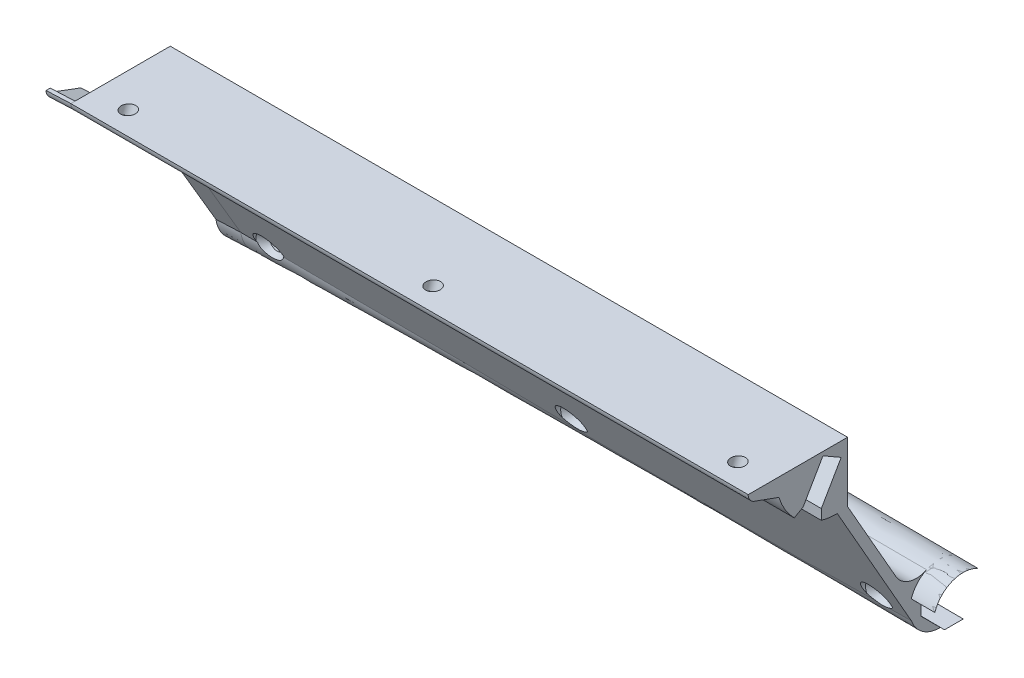
SolidWorks part; units mm, degrees
ref_plane "Front Plane" through (0, 0, 0) normal (0, 0, 1) x (1, 0, 0)
ref_plane "Top Plane" through (0, 0, 0) normal (0, 1, 0) x (1, 0, 0)
ref_plane "Right Plane" through (0, 0, 0) normal (1, 0, 0) x (0, 0, -1)
sketch "Sketch1" plane through (0, 0, 0) normal (1, 0, 0) x (0, 0, -1)
  line L0 (-1066.8, -7.5565) -> (1066.8, -7.5565) construction
  line L1 (-101.6, -49.3897) -> (-101.6, -134.0913) construction
  point P0 (-129.3085, -7.5565)
  line B0 (-152.0053, -9.9433) -> (-145.3394, -12.3695)
  line B1 (-138.7918, -17.8795) -> (-133.4197, -8.5759)
  line B2 (-133.4197, -8.5759) -> (-128.4924, -11.4203)
  line B3 (-128.4924, -11.4203) -> (-133.8645, -20.724)
  line B4 (-138.7918, -17.8795) -> (-141.1886, -19.2631)
  line B5 (-151.1366, -10.0965) -> (-145.86, -10.0965)
  line B6 (-146.0566, -7.5565) -> (-153.6766, -7.5565)
  line B7 (-146.0566, -7.5565) -> (-126.7512, -7.5565)
  line B8 (-126.7512, -23.8281) -> (-126.7512, -7.5565)
  line B9 (-133.8645, -20.724) -> (-133.8646, -23.4918)
  arc B10 (-145.86, -10.0965) -> (-141.1886, -19.2631) centre (-129.5466, -7.5565) ccw
  arc B11 (-153.6766, -7.5565) -> (-151.1366, -10.0965) centre (-151.1366, -7.5565) ccw
  arc B12 (-133.8646, -23.4918) -> (-126.7512, -23.8281) centre (-129.5466, -7.5565) ccw
  dimension "D1" = 25.1512
sketch_block_instance "Rear LED Sketch Block1-1"
sketch_block "Rear LED Sketch Block1" parameters "D1"=20
extrude "Boss-Extrude1" add sketch "Sketch1" along normal mid plane 190.5 contours B9 B12 B8 B7 B6 B11 B5 B10 B4 B1 B2 B3 | B11 B0 B10 B5
sketch "Sketch4" plane through (0, 0, 0) normal (1, 0, 0) x (0, 0, -1)
  line L0 (-106.68, -54.2581) -> (-101.6, -54.2581)
  line L1 (-106.68, -54.2581) -> (-101.6, -54.2581)
  line L2 (-106.68, -54.2581) -> (-106.68, -58.9572)
  line L3 (-106.68, -54.2581) -> (-106.68, -58.9572)
sketch "Sketch2" plane through (0, 0, 0) normal (1, 0, 0) x (0, 0, -1)
  line L2 (-106.68, -54.2581) -> (-101.6, -54.2581) construction
  line L3 (-106.68, -54.2581) -> (-106.68, -58.9572) construction
  line B0 (-101.7905, -59.1476) -> (-101.7905, -64.4689)
  line B1 (-101.7905, -59.1476) -> (-106.8705, -59.1476)
  line B2 (-106.8705, -54.0676) -> (-106.8705, -59.1476)
  line B3 (-106.8705, -54.0676) -> (-101.7905, -54.0676)
  line B4 (-101.7905, -49.2924) -> (-101.7905, -54.0676)
  line B5 (-101.7905, -49.2924) -> (-97.79, -49.2924)
  arc B6 (-97.79, -49.2924) -> (-101.7905, -64.4689) centre (-101.7905, -56.3534) ccw
  dimension "D1" = 0.1905
  dimension "D2" = 0.1905
sketch_block_instance "Rear LED Sketch Block2-1"
sketch_block "Rear LED Sketch Block2"
sketch "Sketch3" plane through (0, 0, 101.6) normal (0, 0, 1) x (1, 0, 0)
  arc A0 (372.8943, -70.8558) -> (-885.4187, -145.1541) centre (30.2426, -4960.2394) ccw construction
  arc A1 (372.8943, -70.8558) -> (-885.4187, -145.1541) centre (30.2426, -4960.2394) ccw
sweep "Sweep1" add profiles "Sketch2" path "Sketch3"
ref_plane "Plane1" through (-95.25, 0, 0) normal (-1, 0, 0) x (0, 0, 1)
ref_plane "Plane2" through (95.25, 0, 0) normal (1, 0, 0) x (0, 0, -1)
other "SurfaceCut1"
other "SurfaceCut3"
ref_plane "Plane4" through (-94.6651, -4.0865, 0) normal (0.9991, 0.0431, 0) x (0, 0, -1)
sketch "Sketch5" plane through (0, 0, 0) normal (1, 0, 0) x (0, 0, -1)
  line L0 (-129.675, -23.8281) -> (-108.8408, -60.3728)
  line L1 (-106.8705, -58.7002) -> (-126.7512, -23.8281)
  line L2 (-126.7512, -23.8281) -> (-126.7512, -7.5565) construction
  line L3 (-126.7512, -23.8281) -> (-129.675, -23.8281)
  line L4 (-108.8408, -60.3728) -> (-106.8705, -60.3728)
  line L5 (-106.8705, -60.3728) -> (-106.8705, -58.7002)
  line L6 (-106.8705, -54.0676) -> (-106.8705, -59.1476) construction
  arc A0 (-97.79, -49.2924) -> (-101.7905, -64.4689) centre (-101.7905, -56.3534) ccw construction
  dimension "D1" = 2.54
extrude "Boss-Extrude2" add sketch "Sketch5" along normal up to surface and the other way up to surface
other "SurfaceCut5"
sketch "Sketch6" plane through (-94.6651, -4.0865, 0) normal (-0.9991, -0.0431, 0) x (0, 0, 1)
  line L0 (101.7905, -56.5507) -> (101.7905, -61.8728) construction
  line L1 (153.6766, -3.4732) -> (126.7512, -3.4732) construction
  line L2 (152.0053, -5.8623) -> (145.3394, -8.2907) construction
  line L3 (129.5391, -19.9986) -> (109.8687, -54.534) construction
  line L4 (101.7905, -56.5507) -> (101.7905, -61.8728)
  line L5 (153.6766, -3.4732) -> (126.7512, -3.4732)
  line L6 (152.0053, -5.8623) -> (145.3394, -8.2907)
  line L7 (129.5391, -19.9986) -> (109.8687, -54.534)
  line L8 (128.8829, -18.8412) -> (108.7495, -54.1895)
  line L9 (151.614, -4.7883) -> (144.4001, -7.4164)
  line L10 (138.7918, -13.8058) -> (141.1886, -15.1907) construction
  line L11 (133.8645, -16.6529) -> (133.8646, -19.4234) construction
  line L12 (140.1634, -14.5984) -> (141.1886, -15.1907)
  line L13 (133.8646, -18.2391) -> (133.8646, -19.4234)
  line L14 (133.5654, -18.3202) -> (133.8646, -18.2391)
  line L15 (140.3822, -14.3806) -> (140.1634, -14.5984)
  ellipse E0 centre (151.1366, -3.4732) end of major axis (151.1366, -0.9308) minor radius 2.54 (152.0053, -5.8623) -> (153.6766, -3.4732) ccw construction
  ellipse E1 centre (129.5466, -3.4732) end of major axis (129.5466, -19.9986) minor radius 16.51 (141.1886, -15.1907) -> (145.3394, -8.2907) ccw construction
  ellipse E2 centre (129.5466, -3.4732) end of major axis (129.5466, -19.9986) minor radius 16.51 (129.5391, -19.9986) -> (133.8646, -19.4234) ccw construction
  ellipse E3 centre (151.1366, -3.4732) end of major axis (151.1366, -0.9308) minor radius 2.54 (152.0053, -5.8623) -> (153.6766, -3.4732) ccw
  ellipse E4 centre (129.5466, -3.4732) end of major axis (129.5466, -19.9986) minor radius 16.51 (141.1886, -15.1907) -> (145.3394, -8.2907) ccw
  ellipse E5 centre (129.5466, -3.4732) end of major axis (129.5466, -19.9986) minor radius 16.51 (129.5391, -19.9986) -> (133.8646, -19.4234) ccw
  spline S0 degree 3 poles (-155.2589, 904.5233) (13.2066, 99.2717) (72.9154, -67.3921) (103.5206, -61.6901) (103.7625, -61.6335) (104.2426, -61.4975) (104.4819, -61.4176) (105.1825, -61.1468) (105.6271, -60.9257) (106.2612, -60.5347) (106.467, -60.3945) (106.8673, -60.0935) (107.0617, -59.9327) (107.6156, -59.4296) (107.9506, -59.0637) (108.5527, -58.2714) (108.8209, -57.8411) (109.2671, -56.9519) (109.4481, -56.4899) (115.3533, -36.0633) (46.0699, 14.3305) (-367.4461, -933.2399) knots -7.656413 -7.656413 -7.656413 -7.656413 0.125 0.125 0.1875 0.1875 0.25 0.25 0.375 0.375 0.4375 0.4375 0.5 0.5 0.625 0.625 0.75 0.75 0.875 0.875 6.076436 6.076436 6.076436 6.076436 only from (101.7905, -61.8728) to (109.8687, -54.534) construction
  spline S1 degree 3 poles (101.7905, -61.8728) (102.2937, -61.8728) (102.789, -61.8264) (103.5206, -61.6901) (103.7625, -61.6335) (104.2426, -61.4975) (104.4819, -61.4176) (105.1825, -61.1468) (105.6271, -60.9257) (106.2612, -60.5347) (106.467, -60.3945) (106.8673, -60.0935) (107.0617, -59.9327) (107.6156, -59.4296) (107.9506, -59.0637) (108.5527, -58.2714) (108.8209, -57.8411) (109.2671, -56.9519) (109.4481, -56.4899) (109.7253, -55.5312) (109.8205, -55.0342) (109.8687, -54.534) knots 0 0 0 0 0.125 0.125 0.1875 0.1875 0.25 0.25 0.375 0.375 0.4375 0.4375 0.5 0.5 0.625 0.625 0.75 0.75 0.875 0.875 1 1 1 1
  spline S2 degree 1 poles (101.7905, -60.7298) (108.7495, -54.1895) knots 0 0 1 1 construction
  spline S3 degree 1 poles (128.8829, -18.8412) (133.5654, -18.3202) knots 0 0 1 1 construction
  spline S4 degree 3 poles (101.7905, -60.7298) (102.6619, -60.7298) (104.4225, -60.3954) (106.6781, -58.9596) (108.2494, -56.8015) (108.6958, -55.0607) (108.7495, -54.1895) knots 0 0 0 0 0.255705 0.511411 0.767116 1.022822 1.022822 1.022822 1.022822
  spline S5 degree 3 poles (128.8829, -18.8412) (129.2766, -18.8583) (130.0657, -18.862) (131.2459, -18.7765) (132.4161, -18.6005) (133.1851, -18.4234) (133.5654, -18.3202) knots 3.09839 3.09839 3.09839 3.09839 3.175346 3.252302 3.329258 3.406214 3.406214 3.406214 3.406214
  spline S6 degree 1 poles (140.3822, -14.3806) (144.4001, -7.4164) knots 0 0 1 1 construction
  spline S7 degree 1 poles (151.614, -4.7883) (152.5336, -3.4732) knots 0 0 1 1 construction
  spline S8 degree 3 poles (140.3822, -14.3806) (140.8622, -13.9028) (141.76, -12.8825) (142.8926, -11.1885) (143.7924, -9.3599) (144.2266, -8.0713) (144.4001, -7.4164) knots -2.35896 -2.35896 -2.35896 -2.35896 -2.226725 -2.09449 -1.962254 -1.830019 -1.830019 -1.830019 -1.830019
  spline S9 degree 3 poles (151.614, -4.7883) (151.7472, -4.7398) (152.0001, -4.6011) (152.2985, -4.2888) (152.4897, -3.9012) (152.5336, -3.6152) (152.5336, -3.4732) knots -2.792527 -2.792527 -2.792527 -2.792527 -2.487094 -2.181662 -1.876229 -1.570796 -1.570796 -1.570796 -1.570796
  dimension "D1" = 1.143
extrude "Boss-Extrude3" add sketch "Sketch6" along normal offset from surface (6.731 mm away) 0.381
sketch "Sketch7" plane through (95.25, 0, 0) normal (1, 0, 0) x (0, 0, -1)
  line L16 (-129.5391, -24.0665) -> (-109.5074, -59.2035)
  line L17 (-101.7905, -64.8071) -> (-101.7905, -59.4854)
  line L18 (-101.7905, -59.4854) -> (-106.8705, -59.4854)
  line L19 (-106.8705, -59.4854) -> (-106.8705, -54.4051)
  line L22 (-106.8705, -54.4051) -> (-101.7905, -54.4051)
  line L24 (-101.7905, -54.4051) -> (-101.7905, -49.6295)
  line L26 (-101.7905, -49.6295) -> (-97.79, -49.6295)
  line L27 (-109.4857, -54.113) -> (-126.7512, -23.8281)
  line L50 (-126.7512, -23.8281) -> (-126.7512, -7.5565)
  line L61 (-126.7512, -7.5565) -> (-153.6766, -7.5565)
  line L62 (-152.0053, -9.9433) -> (-145.3394, -12.3695)
  line L63 (-141.1886, -19.2631) -> (-138.7918, -17.8795)
  line L64 (-138.7918, -17.8795) -> (-133.4197, -8.5759)
  line L65 (-133.4197, -8.5759) -> (-128.4924, -11.4203)
  line L66 (-128.4924, -11.4203) -> (-133.8645, -20.724)
  line L67 (-133.8645, -20.724) -> (-133.8646, -23.4918)
  line L68 (-129.5391, -24.0665) -> (-109.5074, -59.2035)
  line L69 (-101.7905, -64.8071) -> (-101.7905, -59.4854)
  line L70 (-101.7905, -59.4854) -> (-106.8705, -59.4854)
  line L71 (-106.8705, -59.4854) -> (-106.8705, -54.4051)
  line L72 (-106.8705, -54.4051) -> (-101.7905, -54.4051)
  line L73 (-101.7905, -54.4051) -> (-101.7905, -49.6295)
  line L74 (-101.7905, -49.6295) -> (-97.79, -49.6295)
  line L75 (-109.4857, -54.113) -> (-126.7512, -23.8281)
  line L76 (-126.7512, -23.8281) -> (-126.7512, -7.5565)
  line L77 (-126.7512, -7.5565) -> (-153.6766, -7.5565)
  line L78 (-152.0053, -9.9433) -> (-145.3394, -12.3695)
  line L79 (-141.1886, -19.2631) -> (-138.7918, -17.8795)
  line L80 (-138.7918, -17.8795) -> (-133.4197, -8.5759)
  line L81 (-133.4197, -8.5759) -> (-128.4924, -11.4203)
  line L82 (-128.4924, -11.4203) -> (-133.8645, -20.724)
  line L83 (-133.8645, -20.724) -> (-133.8646, -23.4918)
  arc A9 (-153.6766, -7.5565) -> (-152.0053, -9.9433) centre (-151.1366, -7.5565) ccw
  arc A10 (-145.3394, -12.3695) -> (-141.1886, -19.2631) centre (-129.5466, -7.5565) ccw
  arc A11 (-133.8646, -23.4918) -> (-129.5391, -24.0665) centre (-129.5466, -7.5565) ccw
  arc A12 (-153.6766, -7.5565) -> (-152.0053, -9.9433) centre (-151.1366, -7.5565) ccw
  arc A13 (-145.3394, -12.3695) -> (-141.1886, -19.2631) centre (-129.5466, -7.5565) ccw
  arc A14 (-133.8646, -23.4918) -> (-129.5391, -24.0665) centre (-129.5466, -7.5565) ccw
  spline S2 degree 3 poles (2567.8604, 1289.2452) (833.2132, 493.0741) (-144.0017, 8.289) (-108.8291, -60.7533) (-108.6035, -61.1213) (-108.1037, -61.8086) (-107.8289, -62.13) (-107.3797, -62.5793) (-107.2238, -62.7236) (-106.8993, -63.0008) (-106.7303, -63.1339) (-106.2132, -63.5093) (-105.8522, -63.7302) (-105.0983, -64.1144) (-104.7029, -64.2785) (-41.9716, -84.6456) (151.7268, 666.5201) (589.7314, 2852.2044) knots -22.581561 -22.581561 -22.581561 -22.581561 0.125 0.125 0.25 0.25 0.375 0.375 0.4375 0.4375 0.5 0.5 0.625 0.625 0.75 0.75 19.917831 19.917831 19.917831 19.917831 only from (-109.5074, -59.2035) to (-101.7905, -64.8071)
  spline S3 degree 3 poles (-1033.1562, -2897.998) (-208.9033, -640.4241) (-44.6823, -65.5493) (-99.7186, -48.8382) (-100.012, -48.7666) (-100.5993, -48.6573) (-101.1886, -48.581) (-101.7821, -48.5695) (-102.3777, -48.5907) (-102.6784, -48.6181) (-103.5656, -48.7489) (-104.1393, -48.8995) (-104.9734, -49.2193) (-105.2487, -49.3426) (-105.7804, -49.6172) (-106.293, -49.9191) (-106.7683, -50.2741) (-107.2249, -50.6559) (-107.445, -50.8615) (-108.0664, -51.5105) (-108.4269, -51.9817) (-108.8886, -52.7452) (-109.0298, -53.0106) (-136.6979, -112.8086) (604.8792, -397.3944) (-3032.056, 599.2618) knots -11.847549 -11.847549 -11.847549 -11.847549 0.125 0.125 0.1875 0.1875 0.25 0.3125 0.3125 0.375 0.375 0.5 0.5 0.5625 0.5625 0.625 0.6875 0.6875 0.75 0.75 0.875 0.875 0.9375 0.9375 14.610125 14.610125 14.610125 14.610125 only from (-97.79, -49.6295) to (-109.4857, -54.113)
  spline S4 degree 3 poles (-109.5074, -59.2035) (-109.3761, -59.6067) (-109.2142, -59.9973) (-108.8291, -60.7533) (-108.6035, -61.1213) (-108.1037, -61.8086) (-107.8289, -62.13) (-107.3797, -62.5793) (-107.2238, -62.7236) (-106.8993, -63.0008) (-106.7303, -63.1339) (-106.2132, -63.5093) (-105.8522, -63.7302) (-105.0983, -64.1144) (-104.7029, -64.2785) (-103.4836, -64.6744) (-102.6483, -64.8071) (-101.7905, -64.8071) knots 0 0 0 0 0.125 0.125 0.25 0.25 0.375 0.375 0.4375 0.4375 0.5 0.5 0.625 0.625 0.75 0.75 1 1 1 1
  spline S5 degree 3 poles (-97.79, -49.6295) (-98.3134, -49.333) (-98.8611, -49.0986) (-99.7186, -48.8382) (-100.012, -48.7666) (-100.5993, -48.6573) (-101.1886, -48.581) (-101.7821, -48.5695) (-102.3777, -48.5907) (-102.6784, -48.6181) (-103.5656, -48.7489) (-104.1393, -48.8995) (-104.9734, -49.2193) (-105.2487, -49.3426) (-105.7804, -49.6172) (-106.293, -49.9191) (-106.7683, -50.2741) (-107.2249, -50.6559) (-107.445, -50.8615) (-108.0664, -51.5105) (-108.4269, -51.9817) (-108.8886, -52.7452) (-109.0298, -53.0106) (-109.2816, -53.5548) (-109.3915, -53.8316) (-109.4857, -54.113) knots 0 0 0 0 0.125 0.125 0.1875 0.1875 0.25 0.3125 0.3125 0.375 0.375 0.5 0.5 0.5625 0.5625 0.625 0.6875 0.6875 0.75 0.75 0.875 0.875 0.9375 0.9375 1 1 1 1
  dimension "D1" = 0
extrude "Cut-Extrude1" cut sketch "Sketch7" against normal blind 6.35
sketch "Sketch8" plane through (0, 0, 106.8705) normal (0, 0, -1) x (-1, 0, 0)
  arc A2 (92.2896, -58.0454) -> (-88.9304, -56.8655) centre (-30.2426, -4960.2394) ccw
  arc A3 (92.2896, -58.0454) -> (-88.9304, -56.8655) centre (-30.2426, -4960.2394) ccw
  point P0 (-80.8649, -56.7756)
  point P1 (1.6851, -56.6182)
  point P2 (84.2351, -57.8507)
  dimension "D2" = 82.55
  dimension "D3" = 82.55
  dimension "D1" = 2.54
sketch "Sketch9" plane through (0, 0, 106.8705) normal (0, 0, -1) x (-1, 0, 0)
  point P0 (-80.8649, -56.7756)
  point P1 (1.6851, -56.6182)
  point P3 (84.2351, -57.8507)
ref_plane "Plane5" through (80.8649, 0, 0) normal (1, 0, 0) x (0, 0, -1)
fillet "Fillet1" radius 6.35 1 edges at (46.559, -53.9689, 109.5678)
sketch "Sketch10" plane through (80.8649, 0, 0) normal (1, 0, 0) x (0, 0, -1)
  line L0 (-106.8705, -58.6806) -> (-106.8705, -56.7756)
  line L1 (-106.8705, -56.7756) -> (-113.2205, -56.7756)
  line L2 (-113.2205, -56.7756) -> (-113.2205, -60.5856)
  line L3 (-113.2205, -60.5856) -> (-110.0455, -60.5856)
  line L4 (-110.0455, -60.5856) -> (-108.1405, -58.6806)
  line L5 (-108.1405, -58.6806) -> (-106.8705, -58.6806)
  line L6 (-106.8705, -59.4854) -> (-106.8705, -54.4051) construction
  dimension "D1" = 45
  dimension "D2" = 1.905
  dimension "D3" = 3.81
  dimension "D4" = 1.27
  dimension "D5" = 6.35
revolve "Cut-Revolve1" cut sketch "Sketch10" angle 360 about L1
pattern_sketch "Sketch-Pattern1" of "Cut-Revolve1" driven by "Sketch9"
sketch "Sketch11" plane through (0, -57.6337, 20.977) normal (0, -0.9397, 0.342) x (1, 0, 0)
  line L0 (88.9, 135.8906) -> (-94.3599, 135.8906) construction
  line L1 (88.9, 139.4374) -> (88.9, 132.3438) construction
  line L2 (-94.4122, 139.4374) -> (-94.3075, 132.3438) construction
  point P6 (-2.7299, 135.8906)
  point P7 (79.8201, 135.8906)
  point P8 (-85.2799, 135.8906)
  dimension "D1" = 82.55
  dimension "D2" = 82.55
sketch "Sketch12" plane through (0, -57.6337, 20.977) normal (0, -0.9397, 0.342) x (1, 0, 0)
  point P0 (79.8201, 135.8906)
  point P1 (-2.7299, 135.8906)
  point P3 (-85.2799, 135.8906)
ref_plane "Plane6" through (-2.7299, 0, 0) normal (1, 0, 0) x (0, 0, -1)
sketch "Sketch13" plane through (-2.7299, 0, 0) normal (1, 0, 0) x (0, 0, -1)
  line L0 (-148.6724, -11.1564) -> (-147.125, -6.905)
  line L1 (-152.0053, -9.9433) -> (-145.3394, -12.3695) construction
  line L2 (-147.125, -6.905) -> (-145.3348, -7.5565)
  line L3 (-145.3348, -7.5565) -> (-146.2307, -10.0178)
  line L4 (-146.2307, -10.0178) -> (-145.0921, -12.4595)
  line L6 (-150.0381, -14.9088) -> (-148.6724, -11.1564)
  line L7 (-152.0053, -9.9433) -> (-145.3394, -12.3695) construction
  line L9 (-145.0921, -12.4595) -> (-146.4579, -16.2119)
  line L10 (-146.4579, -16.2119) -> (-150.0381, -14.9088)
  line L11 (-151.7328, -8.5112) -> (-144.3303, -11.2055) construction
  line L12 (-1093.7253, -7.5565) -> (-1066.8, -7.5565) construction
  point P4 (-148.9211, -10.9278)
  point P8 (-147.3298, -5.4676)
  point P13 (0, 0)
  point P16 (0, 0)
  dimension "D1" = 1.905
  dimension "D2" = 3.81
  dimension "D4" = 45
revolve "Cut-Revolve2" cut sketch "Sketch13" angle 360 about L6
pattern_sketch "Sketch-Pattern2" of "Cut-Revolve2" driven by "Sketch12"
sketch "Sketch14" plane through (0, 0, 126.7512) normal (0, 0, -1) x (-1, 0, 0)
  line L0 (79.6029, -10.0965) -> (-79.6029, -10.0965) construction
  line L1 (-88.9, -7.5565) -> (94.5153, -7.5565) construction
  text T0 "<b>Rear Ceiling LED Strip Mount 5 V1</b>" font "Century Gothic" height 5.08
  point P2 (0, -10.0965)
  point P3 (0, 0)
  point P4 (0, 0)
  point P7 (-79.6029, -10.2385)
  dimension "D1" = 2.54
extrude "Cut-Extrude2" cut sketch "Sketch14" against normal blind 0.635
